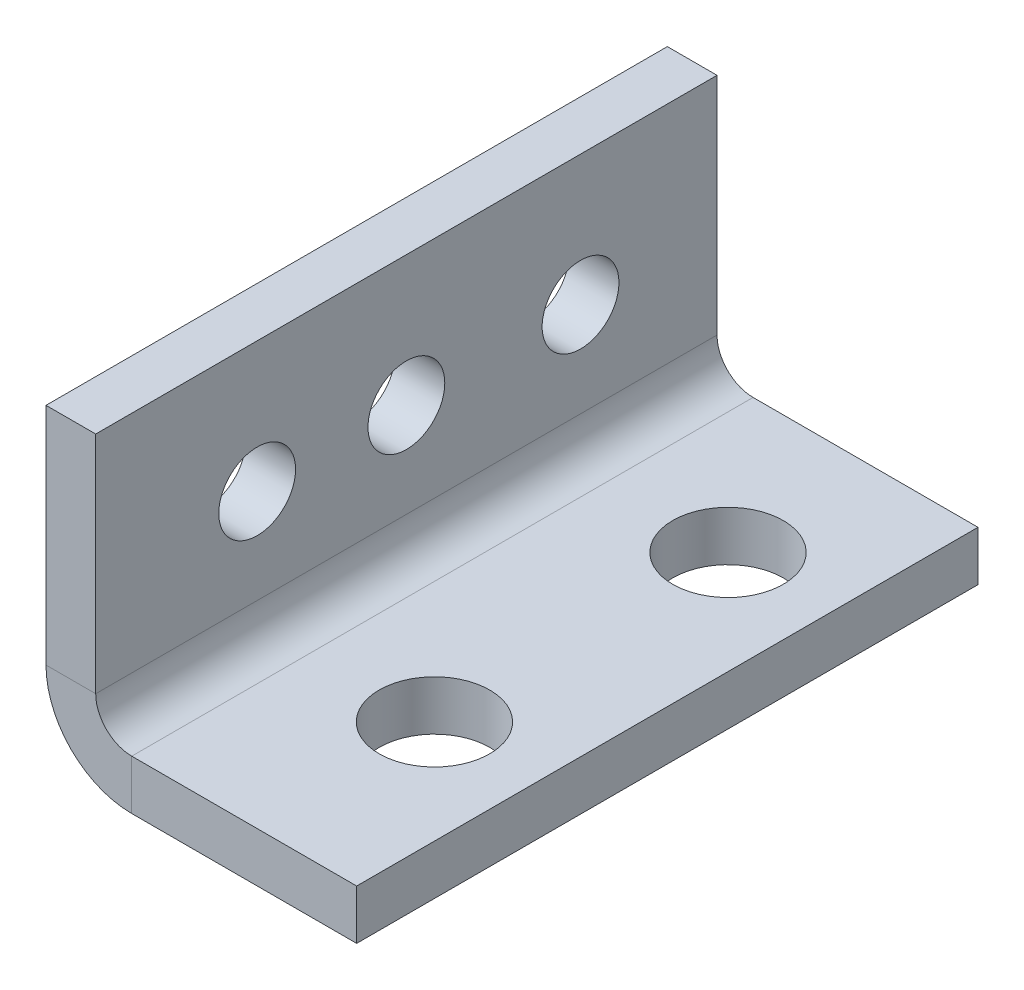
SolidWorks part; units mm, degrees
note: The reader was unsure of these and kept them because the rebuilt part matched: flange length of "Edge-Flange1".
ref_plane "Front Plane" through (0, 0, 0) normal (0, 0, 1) x (1, 0, 0)
ref_plane "Top Plane" through (0, 0, 0) normal (0, 1, 0) x (1, 0, 0)
ref_plane "Right Plane" through (0, 0, 0) normal (1, 0, 0) x (0, 0, -1)
sketch "Sketch1" plane through (0, 0, 0) normal (1, 0, 0) x (0, 0, -1)
  line L0 (0, 0) -> (0, 6.35)
  line L1 (0, 6.35) -> (12.7, 6.35)
  line L2 (12.7, 6.35) -> (12.7, 0)
  line L3 (12.7, 0) -> (0, 0)
  line L4 (6.35, 6.35) -> (6.35, 0) construction
  line L5 (0, 3.685) -> (12.7, 3.685) construction
  circle A0 centre (3.3, 3.685) radius 0.785
  circle A1 centre (6.35, 3.685) radius 0.785
  circle A2 centre (9.91, 3.685) radius 0.785
  dimension "D2" = 1.57
  dimension "D3" = 3.05
  dimension "D4" = 3.56
  dimension "D1" = 6.35
  dimension "D5" = 12.7
  dimension "D6" = 3.685
base flange "Base-Flange1" sketch "Sketch1" thickness 1.016 reverse thickness direction no parameters "D1"=0.7366
edge flange "Edge-Flange1" sketch "Sketch8" flange angle 90 flange length 6.35 flange position material inside bend radius 0.7366 thickness 1.016 relief rectangular parameters "D6"=10
sketch "Sketch8" plane through (0, 0, 0) normal (0, -1, 0) x (0, 0, -1)
  line L0 (0, 0) -> (12.7, 0) construction
  line L1 (0, 0) -> (12.7, 0)
  line L2 (0, 0) -> (0, 5.334)
  line L3 (0, 5.334) -> (12.7, 5.334)
  line L4 (12.7, 5.334) -> (12.7, 0)
bend "EdgeBend1" bend radius 0.7366 bend angle 90 parameters "D5"=1
sketch "Sketch9" plane through (0, 1.016, 0) normal (0, 1, 0) x (1, 0, 0)
  line L0 (0.7366, 12.7) -> (5.334, 12.7) construction
  line L1 (-1.016, 12.7) -> (-1.016, 0) construction
  line L2 (3.224, 9.7) -> (3.224, 3.7) construction
  circle A0 centre (3.224, 3.7) radius 1.13
  circle A1 centre (3.224, 9.7) radius 1.13
  dimension "D3" = 2.26
  dimension "D1" = 3
  dimension "D2" = 6
  dimension "D4" = 4.24
extrude "Cut-Extrude1" cut sketch "Sketch9" against normal up to next normal cut yes
sketch "Bend-Lines1" [suppressed] plane through (0, 0, 0) normal (0, 1, 0) x (1, 0, 0)
sketch "Bounding-Box1" [suppressed] plane through (0, 0, 0) normal (0, 1, 0) x (1, 0, 0)
sheet metal parameters "Sheet-Metal1" thickness 1.016 parameters "D1"=0.7366
flat pattern "Flat-Pattern1" [suppressed]
sketch "Bend-Lines2" plane through (0, 0, 0) normal (0, 1, 0) x (1, 0, 0)
sketch "Bounding-Box2" [suppressed] plane through (0, 0, 0) normal (0, 1, 0) x (1, 0, 0)
sheet metal parameters "Sheet-Metal2" thickness 1.016 parameters "D1"=0.7366
flat pattern "Flat-Pattern1" [suppressed]
sketch "Bend-Lines2" plane through (0, 0, 0) normal (0, 1, 0) x (1, 0, 0)
sketch "Bounding-Box2" [suppressed] plane through (0, 0, 0) normal (0, 1, 0) x (1, 0, 0)
bend of the flat pattern "Flatten-<EdgeBend1>1"
sheet metal parameters "Sheet-Metal3" thickness 1.016 parameters "D1"=0.7366
flat pattern "Flat-Pattern1"
sketch "Bend-Lines2" plane through (0, 0, 0) normal (1, 0, 0) x (0, 0, -1)
  line L0 (0, 0.7751) -> (12.7, 0.7751) construction
  line L1 (0, 0.7751) -> (12.7, 0.7751) construction
sketch3d "Bounding-Box2" [suppressed]
  line L0 (12.7, -4.7998, 0) -> (0, -4.7998, 0) construction
  line L1 (12.7, 6.35, 0) -> (0, 6.35, 0) construction
  line L2 (12.7, -4.7998, 0) -> (12.7, 6.35, 0) construction
  line L3 (0, -4.7998, 0) -> (0, 6.35, 0) construction
bend of the flat pattern "Flatten-<EdgeBend1>1"
